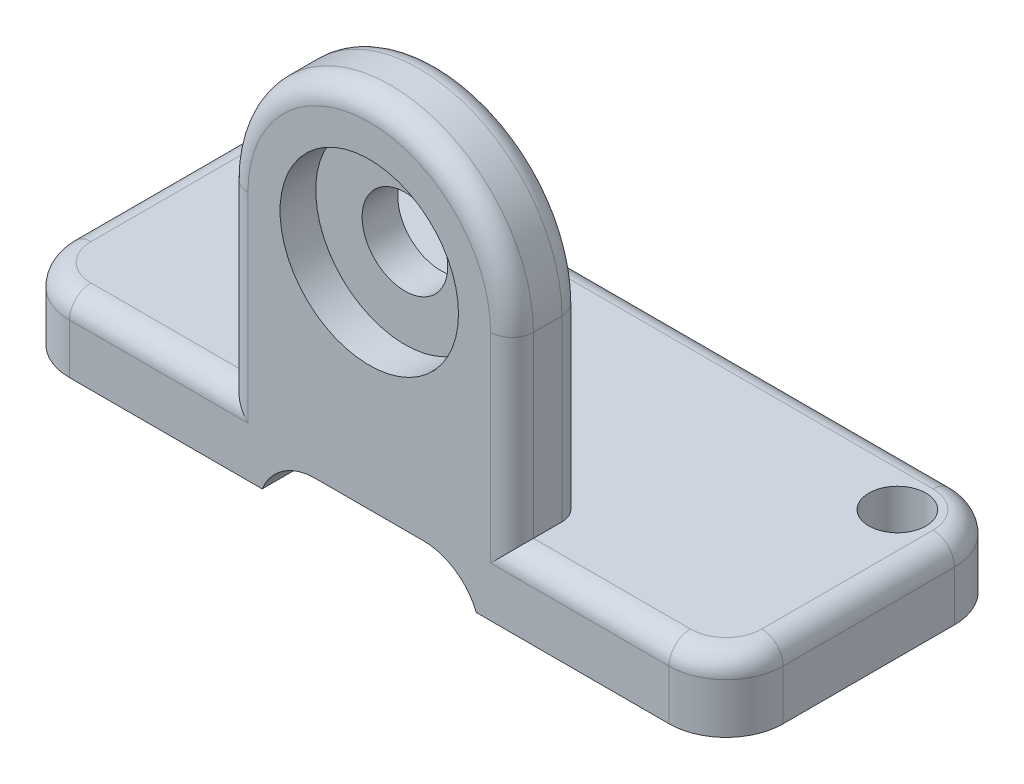
SolidWorks part; units mm, degrees
ref_plane "Спереди" through (0, 0, 0) normal (0, 0, 1) x (1, 0, 0)
ref_plane "Сверху" through (0, 0, 0) normal (0, 1, 0) x (1, 0, 0)
ref_plane "Справа" through (0, 0, 0) normal (1, 0, 0) x (0, 0, -1)
sketch "Эскиз1" plane through (0, 0, 0) normal (0, 1, 0) x (1, 0, 0)
  line L1 (-50, -20) -> (50, -20)
  line L2 (-50, -20) -> (-50, 20)
  line L3 (-50, 20) -> (50, 20)
  line L4 (50, -20) -> (50, 20)
  line L5 (-50, -20) -> (50, 20) construction
  line L6 (-50, 20) -> (50, -20) construction
  point P0 (0, 0)
  dimension "D1" = 40
  dimension "D2" = 100
extrude "Бобышка-Вытянуть1" add sketch "Эскиз1" along normal blind 10
sketch "Эскиз2" plane through (0, 0, 20) normal (0, 0, 1) x (1, 0, 0)
  line L0 (-20, 0) -> (-20, 35)
  line L1 (-50, 0) -> (50, 0) construction
  line L2 (20, 0) -> (20, 35)
  line L3 (-20, 0) -> (20, 0)
  arc A0 (-20, 35) -> (20, 35) centre (0, 35) cw
  dimension "D1" = 20
  dimension "D2" = 50
  dimension "D3" = 35
extrude "Бобышка-Вытянуть2" add sketch "Эскиз2" against normal blind 10 contours L3 L2 A0 L0
sketch "Эскиз3" plane through (0, 0, 20) normal (0, 0, 1) x (1, 0, 0)
  circle A0 centre (0, 35) radius 12.5
  dimension "D1" = 25
extrude "Вырез-Вытянуть1" cut sketch "Эскиз3" against normal blind 5
sketch "Эскиз7" plane through (0, 0, 15) normal (0, 0, 1) x (1, 0, 0)
  circle A0 centre (0, 35) radius 6
  dimension "D1" = 12
extrude "Вырез-Вытянуть2" cut sketch "Эскиз7" against normal blind 5 contours A0
sketch "Эскиз10" plane through (0, 0, 20) normal (0, 0, 1) x (1, 0, 0)
  line L0 (-15, 0) -> (-15, 5)
  line L1 (-50, 0) -> (50, 0) construction
  line L2 (-15, 5) -> (15, 5)
  line L3 (15, 5) -> (15, 0)
  line L4 (-15, 0) -> (15, 0)
  dimension "D1" = 30
  dimension "D2" = 35
  dimension "D3" = 5
extrude "Вырез-Вытянуть3" cut sketch "Эскиз10" against normal through all contours L4 L3 L2 L0
sketch "Эскиз14" plane through (0, 10, 0) normal (0, 1, 0) x (1, 0, 0)
  line L0 (0, 20) -> (0, -20) construction
  line L1 (50, 20) -> (-50, 20) construction
  line L2 (-20, -20) -> (20, -20) construction
  circle A0 centre (-42, 12) radius 4
  circle A1 centre (42, 12) radius 4
  dimension "D3" = 8
  dimension "D1" = 84
  dimension "D2" = 8
extrude "Вырез-Вытянуть4" cut sketch "Эскиз14" against normal through all
fillet "Скругление2" radius 8 6 edges at (-15, 5, 0) (15, 5, 0) (50, 5, 20) (-50, 5, 20) (-50, 5, -20) (50, 5, -20)
fillet "Скругление3" radius 3 15 edges at (20, 22.5, 10) (-20, 22.5, 10) (-47.6569, 10, -17.6569) (-20, 22.5, 20) (0, 55, 10) (0, 55, 20) (20, 22.5, 20) (-50, 10, 0) (-47.6569, 10, 17.6569) (-31, 10, 20) (0, 10, -20) (47.6569, 10, -17.6569) (50, 10, 0) (47.6569, 10, 17.6569) (31, 10, 20)
